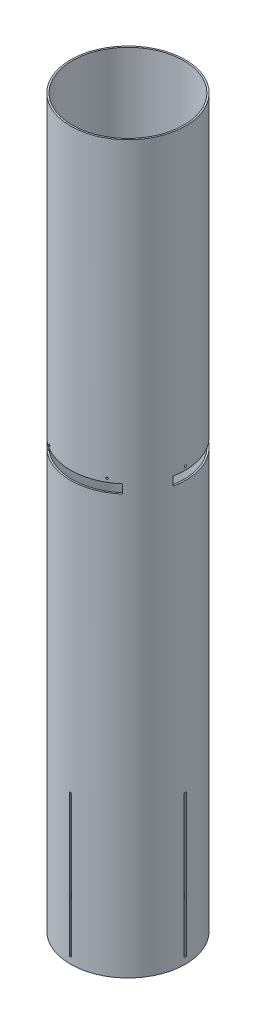
SolidWorks part; units mm, degrees
material "A-Glass Fiber"
ref_plane "Front Plane" through (0, 0, 0) normal (0, 0, 1) x (1, 0, 0)
ref_plane "Top Plane" through (0, 0, 0) normal (0, 1, 0) x (1, 0, 0)
ref_plane "Right Plane" through (0, 0, 0) normal (1, 0, 0) x (0, 0, -1)
sketch "Sketch1" plane through (0, 0, 0) normal (0, 1, 0) x (1, 0, 0)
  circle A0 centre (0, 0) radius 76.2
  circle A1 centre (0, 0) radius 78.359
  dimension "D1" = 152.4
  dimension "D2" = 156.718
extrude "Boss-Extrude1" add sketch "Sketch1" along normal blind 990.6
ref_plane "Plane1" through (0, 0, 0) normal (0.7071, 0, 0.7071) x (0.7071, 0, -0.7071)
ref_axis "Axis1" through (0, 990.6, 0) along (0, -1, 0)
sketch "Sketch2" plane through (0, 0, 0) normal (1, 0, 0) x (0, 0, -1)
  line L0 (0, 0) -> (0, 8.89)
  line L1 (1.5875, 8.89) -> (-1.5875, 8.89)
  line L2 (1.5875, 8.89) -> (1.5875, 203.2)
  line L3 (1.5875, 203.2) -> (-1.5875, 203.2)
  line L4 (-1.5875, 8.89) -> (-1.5875, 203.2)
  line L5 (1.5875, 8.89) -> (-1.5875, 203.2) construction
  line L6 (1.5875, 203.2) -> (-1.5875, 8.89) construction
  line L7 (78.359, 990.6) -> (-78.359, 990.6) construction
  line L8 (78.359, 990.6) -> (-78.359, 990.6)
  line L9 (0, 990.6) -> (0, 588.645)
  line L10 (-78.359, 0) -> (78.359, 0) construction
  circle A0 centre (0, 588.645) radius 1.3525
  point P0 (0, 106.045)
  dimension "D4" = 2.7051
  dimension "D1" = 3.175
  dimension "D2" = 194.31
  dimension "D5" = 588.645
  dimension "D3" = 203.2
extrude "Cut-Extrude1" cut sketch "Sketch2" against normal through all contours L4 L1 L2 L3 region at (0, 106.045, 0)
pattern_circular "CirPattern1" count 4 over 360 about axis through (0, 0, 0) along (0, 1, 0) of "Cut-Extrude1" reverse direction yes
extrude "Cut-Extrude2" cut sketch "Sketch2<3>" against normal through all contours A0 region at (0, 587.7157, 0.9293)
sketch "Sketch2<3>" plane through (0, 0, 0) normal (1, 0, 0) x (0, 0, -1) same geometry as "Sketch2"
pattern_circular "CirPattern2" count 6 over 360 about axis through (0, 990.6, 0) along (0, -1, 0) of "Cut-Extrude2"
sketch "Sketch3" plane through (0, 0, 0) normal (0.7071, 0, 0.7071) x (0.7071, 0, -0.7071)
  line L0 (0, 0) -> (0, 127) construction
  circle A0 centre (0, 127) radius 3.175
  dimension "D1" = 6.35
  dimension "D2" = 127
extrude "Cut-Extrude3" cut sketch "Sketch3" against normal through all
ref_plane "Plane3" through (0, 583.8825, 0) normal (0, 1, 0) x (1, 0, 0)
sketch "Sketch7" plane through (0, 583.8825, 0) normal (0, 1, 0) x (1, 0, 0)
  line L0 (0, 0) -> (-76.8534, -15.2871)
  line L1 (0, 0) -> (0, 93.232) construction
  line L2 (0, 0) -> (-25.1877, 74.2005)
  line L3 (-78.359, 0) -> (0, 0) construction
  arc A0 (-78.3473, 1.3526) -> (-78.3473, -1.3525) centre (0, 0) ccw construction
  circle A1 centre (0, 0) radius 76.2 construction
  circle A2 centre (0, 0) radius 78.359
  circle A3 centre (0, 0) radius 78.359
  circle A4 centre (0, 0) radius 76.2
  circle A5 centre (0, 0) radius 78.359 construction
  arc A6 (-38.0023, 68.527) -> (-40.345, 67.1745) centre (0, 0) ccw construction
  arc A7 (-78.3473, 1.3526) -> (-78.3473, -1.3525) centre (0, 0) ccw
  arc A8 (-38.0023, 68.527) -> (-40.345, 67.1745) centre (0, 0) ccw
  dimension "D1" = 82.5
  dimension "D3" = 11.25
  dimension "D2" = 0
extrude "Cut-Extrude4" cut sketch "Sketch7" against normal blind 12.065 contours A4 A3 L0 region at (-75.9984, 583.8825, 14.0521)
pattern_circular "CirPattern3" count 3 over 360 about axis through (0, 990.6, 0) along (0, -1, 0) of "Cut-Extrude4"
equation "\"D1@Boss-Extrude1\" = \"Aft_Section_Length\""
equation "\"AB_Coupler_OD_Length\"= 1in"
equation "\"AB_Coupling_Section_Length\"= 0.375in"
equation "\"AB_Coupler_Length\"= \"AB_Coupler_OD_Length\" + \"AB_Coupling_Section_Length\" * 2"
equation "\"AB_Coupler_Num_Screws\"= 6"
equation "\"AB_Coupling_Screw_Diameter\"= 0.1065in"
equation "\"Aft_Section_Length\"= 39in"
equation "\"D4@Sketch2\"=\"AB_Coupling_Screw_Diameter\""
equation "\"D1@CirPattern2\"=\"AB_Coupler_Num_Screws\""
equation "\"Rail_Nut_From_Bottom\"= 5in"
equation "\"Rail_Nut_Diam\"= 0.25in"
equation "\"D1@Sketch3\"=\"Rail_Nut_Diam\""
equation "\"D2@Sketch3\"=\"Rail_Nut_From_Bottom\""
equation "\"AB_BKHD_Thickness\" = 0.375in"
equation "\"AB_Mount_From_Bottom\" = 23.175in"
equation "\"Cutout_Angle\"=80"
